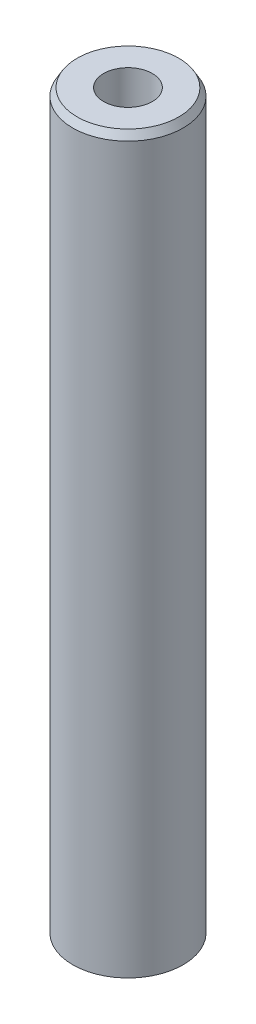
SolidWorks part; units mm, degrees
ref_plane "Front Plane" through (0, 0, 0) normal (0, 0, 1) x (1, 0, 0)
ref_plane "Top Plane" through (0, 0, 0) normal (0, 1, 0) x (1, 0, 0)
ref_plane "Right Plane" through (0, 0, 0) normal (1, 0, 0) x (0, 0, -1)
sketch "Sketch1" plane through (0, 0, 0) normal (0, 1, 0) x (1, 0, 0)
  circle A0 centre (0, 0) radius 10
  dimension "SHAFT_OD" = 20
extrude "Boss-Extrude1" add sketch "Sketch1" along normal blind 133.3876
sketch "Sketch2" plane through (0, 0, 0) normal (0, 1, 0) x (1, 0, 0)
  circle A0 centre (0, 0) radius 4.4123
  dimension "BORE_D" = 8.8246
extrude "Cut-Extrude1" cut sketch "Sketch2" along normal through all
chamfer "Chamfer1" distance 1.3501 angle 30.213 2 edges at (0, 133.3876, 10) (0, 0, 10) first distance on face at (0, 133.3876, 10) first distance on face at (0, 0, 4.4123)
